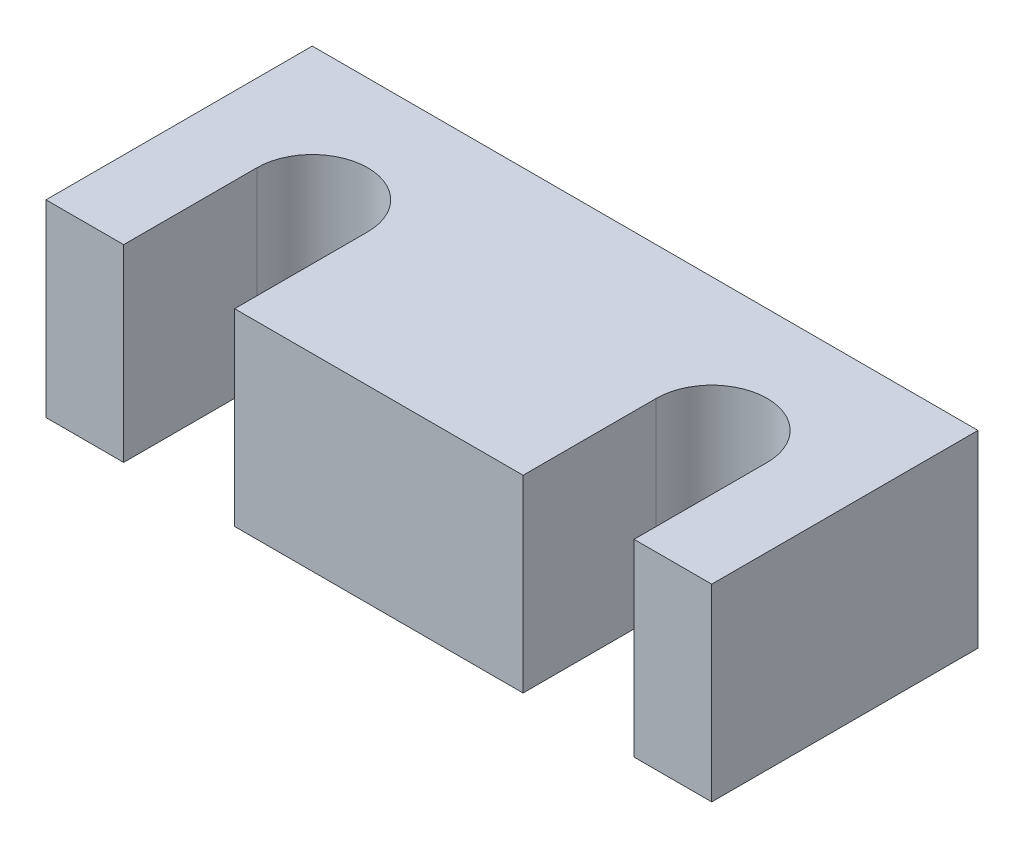
SolidWorks part; units mm, degrees
ref_plane "Front Plane" through (0, 0, 0) normal (0, 0, 1) x (1, 0, 0)
ref_plane "Top Plane" through (0, 0, 0) normal (0, 1, 0) x (1, 0, 0)
ref_plane "Right Plane" through (0, 0, 0) normal (1, 0, 0) x (0, 0, -1)
sketch "Sketch1" plane through (0, 0, 0) normal (0, 1, 0) x (1, 0, 0)
  line L1 (15, 6) -> (-15, 6)
  line L2 (15, 6) -> (15, -6)
  line L3 (15, -6) -> (-15, -6)
  line L4 (-15, 6) -> (-15, -6)
  line L5 (0, -6) -> (0, 6) construction
  line L6 (15, 0) -> (-15, 0) construction
  point P0 (0, 0)
  dimension "D1" = 30
  dimension "D2" = 12
extrude "Boss-Extrude1" add sketch "Sketch1" along normal blind 8.5
sketch "Sketch2" plane through (0, 8.5, 0) normal (0, 1, 0) x (1, 0, 0)
  line L0 (9, 0) -> (-9, 0) construction
  circle A0 centre (-9, 0) radius 1.5
  circle A1 centre (9, 0) radius 1.5
  point P4 (0, 0)
  dimension "D1" = 3
  dimension "D2" = 18
extrude "Cut-Extrude1" cut sketch "Sketch2" against normal through all
sketch "Sketch3" plane through (0, 8.5, 0) normal (0, 1, 0) x (1, 0, 0)
  line L0 (-9, 0) -> (-9, -6) construction
  line L1 (-15, -6) -> (15, -6) construction
  line L2 (-6.5, 0) -> (-6.5, -6)
  line L3 (-11.5, 0) -> (-11.5, -6)
  line L4 (9, 0) -> (9, -6) construction
  line L5 (11.5, 0) -> (11.5, -6)
  line L6 (6.5, 0) -> (6.5, -6)
  arc A0 (-6.5, 0) -> (-11.5, 0) centre (-9, 0) ccw
  arc A1 (-11.5, -6) -> (-6.5, -6) centre (-9, -6) ccw
  arc A2 (11.5, 0) -> (6.5, 0) centre (9, 0) ccw
  arc A3 (6.5, -6) -> (11.5, -6) centre (9, -6) ccw
  point P5 (-9, -3)
  point P10 (9, -3)
  dimension "D1" = 5
  dimension "D2" = 6
extrude "Cut-Extrude2" cut sketch "Sketch3" against normal through all
sketch "Sketch4" plane through (0, 0, 0) normal (0, -1, 0) x (1, 0, 0)
  line L0 (0, -6) -> (0, 0) construction
  line L1 (15, -6) -> (-15, -6) construction
  line L2 (-6, -6) -> (-6, 0)
  line L3 (6, -6) -> (6, 0)
  arc A0 (-6, -6) -> (6, -6) centre (0, -6) ccw
  arc A1 (6, 0) -> (-6, 0) centre (0, 0) ccw
  point P5 (0, -3)
  dimension "D1" = 12
  dimension "D2" = 6
extrude "Boss-Extrude2" add sketch "Sketch4" against normal blind 2
